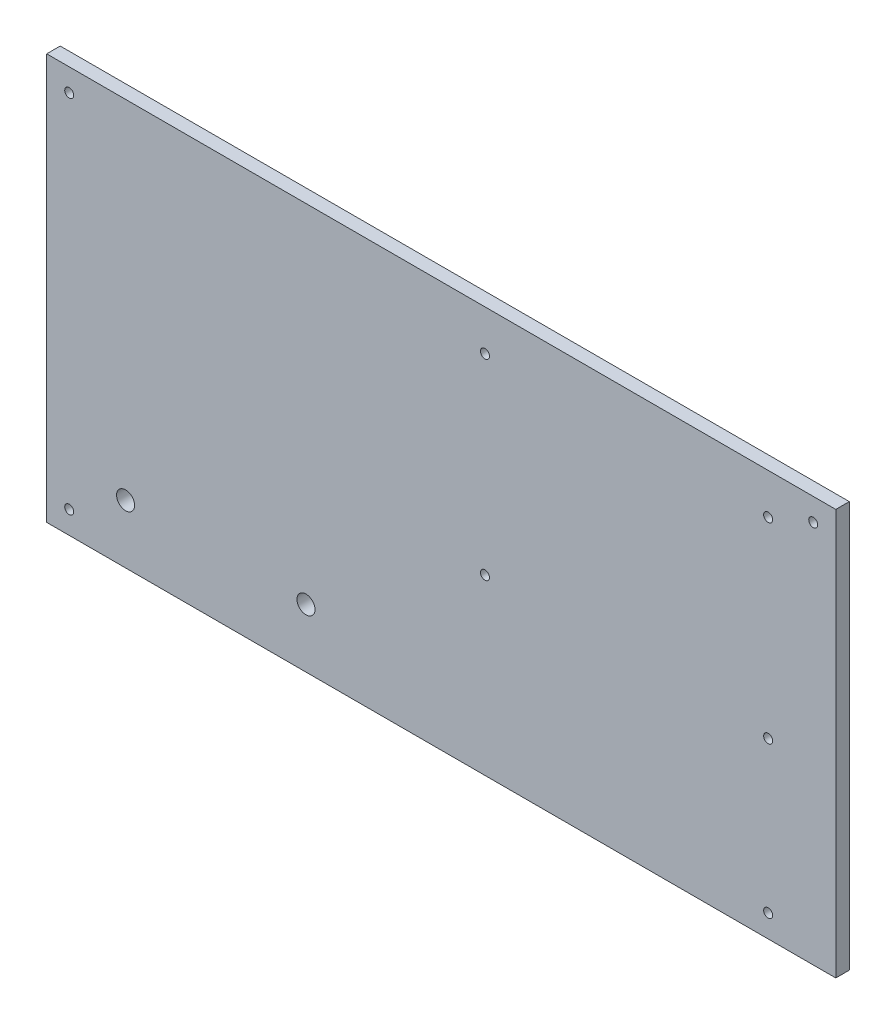
SolidWorks part; units mm, degrees
material "Faia"
ref_plane "Plano frontal" through (0, 0, 0) normal (0, 0, 1) x (1, 0, 0)
ref_plane "Plano superior" through (0, 0, 0) normal (0, 1, 0) x (1, 0, 0)
ref_plane "Plano direito" through (0, 0, 0) normal (1, 0, 0) x (0, 0, -1)
sketch "Esboço1" plane through (0, 0, 0) normal (0, 0, 1) x (1, 0, 0)
  line L0 (175, 0) -> (-175, 0) construction
  line L1 (-175, 90) -> (175, 90)
  line L2 (-175, 90) -> (-175, -90)
  line L3 (-175, -90) -> (175, -90)
  line L4 (175, 90) -> (175, -90)
  line L5 (-175, 90) -> (175, -90) construction
  line L6 (-175, -90) -> (175, 90) construction
  line L7 (165, 80) -> (165, 90) construction
  line L8 (145, -80) -> (145, -90) construction
  line L9 (-140, -64) -> (-60, -64) construction
  circle A0 centre (145, -80) radius 2
  circle A1 centre (165, 80) radius 2
  circle A2 centre (-165, 80) radius 2
  circle A3 centre (-165, -80) radius 2
  circle A4 centre (-140, -64) radius 4
  circle A5 centre (-60, -64) radius 4
  point P0 (0, 0)
  point P21 (5, 0)
  point P23 (-100, -64)
  dimension "D5" = 30
  dimension "D8" = 80
  dimension "D10" = 75
  dimension "D3" = 4
  dimension "D11" = 8
  dimension "D1" = 350
  dimension "D2" = 180
  dimension "D4" = 10
  dimension "D7" = 10
  dimension "D9" = 26
  dimension "D6" = 10
extrude "Ressalto-extrusão1" add sketch "Esboço1" along normal blind 6 contours L4 L1 L2 L3 A1 region at (0.164, 0.1024, 0)
sketch "Esboço2" plane through (0, 0, 6) normal (0, 0, 1) x (1, 0, 0)
  line L0 (-175, 90) -> (175, 90) construction
  line L1 (175, 90) -> (175, -90) construction
  circle A0 centre (145, 72) radius 2
  circle A1 centre (19.4, 72) radius 2
  circle A2 centre (19.4, -13) radius 2
  circle A3 centre (145, -13) radius 2
  dimension "D2" = 4
  dimension "D1" = 125.6
  dimension "D3" = 85
  dimension "D4" = 18
  dimension "D5" = 30
extrude "Corte-extrusão1" cut sketch "Esboço2" against normal blind 10
